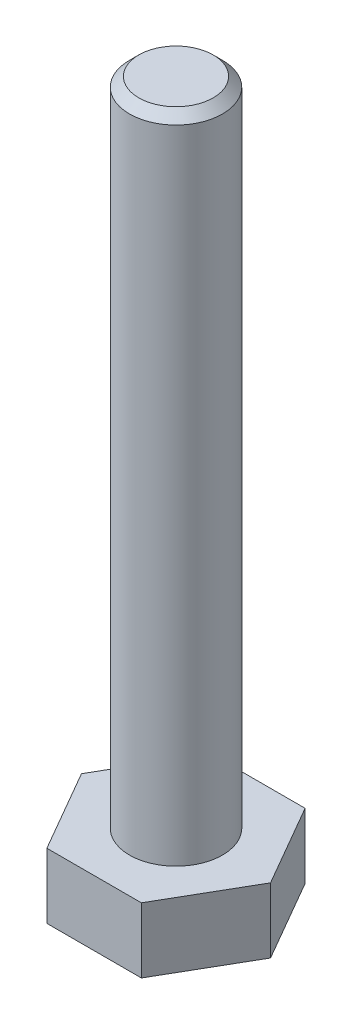
SolidWorks part; units mm, degrees
material "1.6523 (20NiCrMoS2-2)"
ref_plane "Front Plane" through (0, 0, 0) normal (0, 0, 1) x (1, 0, 0)
ref_plane "Top Plane" through (0, 0, 0) normal (0, 1, 0) x (1, 0, 0)
ref_plane "Right Plane" through (0, 0, 0) normal (1, 0, 0) x (0, 0, -1)
sketch "Sketch1" plane through (0, 0, 0) normal (0, 1, 0) x (1, 0, 0)
  line L1 (2.5403, -4.4) -> (5.0807, 0)
  line L2 (5.0807, 0) -> (2.5403, 4.4)
  line L3 (2.5403, 4.4) -> (-2.5403, 4.4)
  line L4 (-2.5403, 4.4) -> (-5.0807, 0)
  line L5 (-5.0807, 0) -> (-2.5403, -4.4)
  line L6 (-2.5403, -4.4) -> (2.5403, -4.4)
  circle A0 centre (0, 0) radius 4.4 construction
  circle A1 centre (0, 0) radius 2.5
  dimension "D1" = 5
  dimension "D2" = 8.8
extrude "Boss-Extrude1" add sketch "Sketch1" along normal blind 3.5 contours A1 | L5 L6 L1 L2 L3 L4 A1 region at (0, 0, 4.2656) region at (0, 0, 0)
extrude "Boss-Extrude2" add sketch "Sketch1<3>" along normal blind 35 from surface contours A1 region at (0, 0, 0) starting at face at (0, 3.5, 0)
sketch "Sketch1<3>" plane through (0, 0, 0) normal (0, 1, 0) x (1, 0, 0) same geometry as "Sketch1"
chamfer "Chamfer1" distance 0.5 angle 45 1 edges at (0, 38.5, 2.5)
